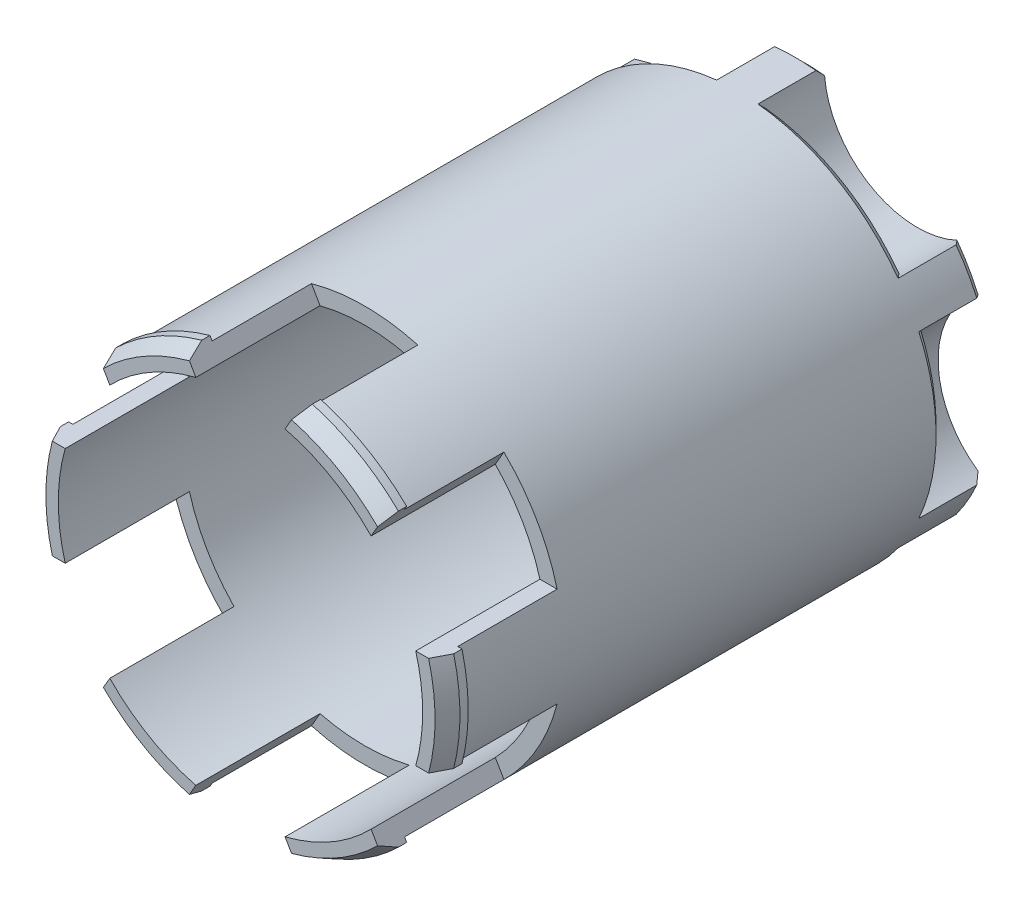
SolidWorks part; units mm, degrees
note: The reader was unsure of these and kept them because the rebuilt part matched: shared geometry of "Sketch1<5>", "Sketch1<7>", "Sketch1<8>", "Sketch1<9>", "Sketch1<10>".
ref_plane "Front Plane" through (0, 0, 0) normal (0, 0, 1) x (1, 0, 0)
ref_plane "Top Plane" through (0, 0, 0) normal (0, 1, 0) x (1, 0, 0)
ref_plane "Right Plane" through (0, 0, 0) normal (1, 0, 0) x (0, 0, -1)
sketch "Sketch1" plane through (0, 0, 0) normal (0, 0, 1) x (1, 0, 0)
  line L0 (-1.4524, 0) -> (71.008, 0) construction
  line L1 (0, 0) -> (0, 72.303) construction
  line L2 (21.166, 6) -> (23.7539, 6)
  line L3 (21.166, -6) -> (23.7539, -6)
  line L4 (15.7792, -15.3303) -> (17.0731, -17.5715)
  line L5 (5.3869, -21.3303) -> (6.6808, -23.5715)
  line L6 (-5.3869, -21.3303) -> (-6.6808, -23.5715)
  line L7 (-15.7792, -15.3303) -> (-17.0731, -17.5715)
  line L8 (-21.166, -6) -> (-23.7539, -6)
  line L9 (-21.166, 6) -> (-23.7539, 6)
  line L10 (-15.7792, 15.3303) -> (-17.0731, 17.5715)
  line L11 (-5.3869, 21.3303) -> (-6.6808, 23.5715)
  line L12 (5.3869, 21.3303) -> (6.6808, 23.5715)
  line L13 (15.7792, 15.3303) -> (17.0731, 17.5715)
  circle A1 centre (0, 0) radius 24
  circle A2 centre (0, 0) radius 22
  arc A3 (21.9216, 9.7695) -> (21.9216, -9.7695) centre (27.5, 0) ccw
  arc A4 (19.358, 10.4532) -> (19.358, -10.4532) centre (27.5, 0) ccw
  circle A5 centre (27.5, 0) radius 13.25 construction
  circle A6 centre (27.5, 0) radius 11.25 construction
  arc A7 (18.7317, -11.5379) -> (0.6262, -21.9911) centre (13.75, -23.8157) ccw
  arc A8 (19.4215, -14.0999) -> (2.5001, -23.8694) centre (13.75, -23.8157) ccw
  arc A9 (-0.6262, -21.9911) -> (-18.7317, -11.5379) centre (-13.75, -23.8157) ccw
  arc A10 (-2.5001, -23.8694) -> (-19.4215, -14.0999) centre (-13.75, -23.8157) ccw
  arc A11 (-19.358, -10.4532) -> (-19.358, 10.4532) centre (-27.5, 0) ccw
  arc A12 (-21.9216, -9.7695) -> (-21.9216, 9.7695) centre (-27.5, 0) ccw
  arc A13 (-18.7317, 11.5379) -> (-0.6262, 21.9911) centre (-13.75, 23.8157) ccw
  arc A14 (-19.4215, 14.0999) -> (-2.5001, 23.8694) centre (-13.75, 23.8157) ccw
  arc A15 (0.6262, 21.9911) -> (18.7317, 11.5379) centre (13.75, 23.8157) ccw
  arc A16 (2.5001, 23.8694) -> (19.4215, 14.0999) centre (13.75, 23.8157) ccw
  arc A17 (16.724, 17.2136) -> (6.5455, 23.0902) centre (0, 0) ccw construction
  circle A18 centre (0, 0) radius 24.5
  point P50 (0, 0)
  point P76 (0, 0)
  dimension "D2" = 22.5
  dimension "D6" = 0
  dimension "D1" = 2
  dimension "D7" = 0.5
  dimension "D3" = 27.5
  dimension "D8" = 12
  dimension "D4" = 2
  dimension "D5" = 6
  dimension "D9" = 6
extrude "Boss-Extrude1" add sketch "Sketch1" along normal blind 3 and the other way blind 43 contours A1 A3 A2 L2 | A2 L3 A1 L2 | A2 A3 A1 L3 | A8 A1 A3 A2 | A1 A8 A2 L4 | A2 L5 A1 L4 | A2 A8 A1 L5 | A10 A1 A8 A2 | A1 A10 A2 L6 | A2 L7 A1 L6 | A2 A10 A1 L7 | A12 A1 A10 A2 | A1 A12 A2 L8 | A2 L9 A1 L8 | A2 A12 A1 L9 | A14 A1 A12 A2 | A1 A14 A2 L10 | A2 L11 A1 L10 | A2 A14 A1 L11 | A16 A1 A14 A2 | A1 A16 A2 L12 | A2 L13 A1 L12 | A2 A16 A1 L13 | A16 A2 A3 A1
extrude "Boss-Extrude2" add sketch "Sketch1<5>" along normal blind 2 from surface at -43 contours A16 A2 A3 A1 | A8 A1 A3 A2 | A10 A1 A8 A2 | A12 A1 A10 A2 | A14 A1 A12 A2 | A16 A1 A14 A2
sketch "Sketch1<5>" plane through (0, 0, 0) normal (0, 0, 1) x (1, 0, 0) same geometry as "Sketch1"
extrude "Boss-Extrude4" add sketch "Sketch1<7>" against normal blind 5 from surface contours A14 A2 A13 | A14 A1 A12 A2 | A12 A2 A11 | A12 A1 A10 A2 | A10 A2 A9 | A10 A1 A8 A2 | A8 A2 A7 | A8 A1 A3 A2 | A2 A4 A3 | A16 A2 A3 A1 | A16 A2 A15 | A16 A1 A14 A2
sketch "Sketch1<7>" plane through (0, 0, 0) normal (0, 0, 1) x (1, 0, 0) same geometry as "Sketch1"
extrude "Boss-Extrude5" add sketch "Sketch1<8>" against normal blind 2 from surface at -48 contours A14 A2 A13 | A16 A1 A14 A2 | A16 A2 A15 | A15 A2 A13 A11 A9 A7 A4 | A2 A4 A3 | A16 A2 A3 A1 | A8 A1 A3 A2 | A8 A2 A7 | A10 A1 A8 A2 | A10 A2 A9 | A12 A1 A10 A2 | A12 A2 A11 | A14 A1 A12 A2 starting at face at (0, 0, -48)
sketch "Sketch1<8>" plane through (0, 0, 0) normal (0, 0, 1) x (1, 0, 0) same geometry as "Sketch1"
chamfer "Chamfer1" distance 1 angle 45 11 edges at (-20.7846, 12, -50) (-20.7846, -12, -50) (0, -24, -50) (20.7846, -12, -50) (20.7846, 12, -50) (0, 24, -50) (24, 0, -43) (12, -20.7846, -43) (-12, -20.7846, -43) (12, 20.7846, -43) (-12, 20.7846, -43)
extrude "Boss-Extrude6" add sketch "Sketch1<9>" along normal blind 15 from surface at 3 contours A2 L3 A1 L2 | A2 L13 A1 L12 | A2 L11 A1 L10 | A2 L9 A1 L8 | A2 L7 A1 L6 | A2 L5 A1 L4 starting at face at (24, 0, 3)
sketch "Sketch1<9>" plane through (0, 0, 0) normal (0, 0, 1) x (1, 0, 0) same geometry as "Sketch1"
extrude "Boss-Extrude7" add sketch "Sketch1<10>" against normal blind 3 from surface at 18 contours L3 A18 L2 A1 | L13 A18 L12 A1 | L11 A18 L10 A1 | L9 A18 L8 A1 | L7 A18 L6 A1 | L5 A18 L4 A1 starting at face at (22.601, 0, 18)
sketch "Sketch1<10>" plane through (0, 0, 0) normal (0, 0, 1) x (1, 0, 0) same geometry as "Sketch1"
chamfer "Chamfer2" distance 2 distance2 1 6 edges at (-12.25, 21.2176, 18) (-24.5, 0, 18) (-12.25, -21.2176, 18) (12.25, -21.2176, 18) (24.5, 0, 18) (12.25, 21.2176, 18)
